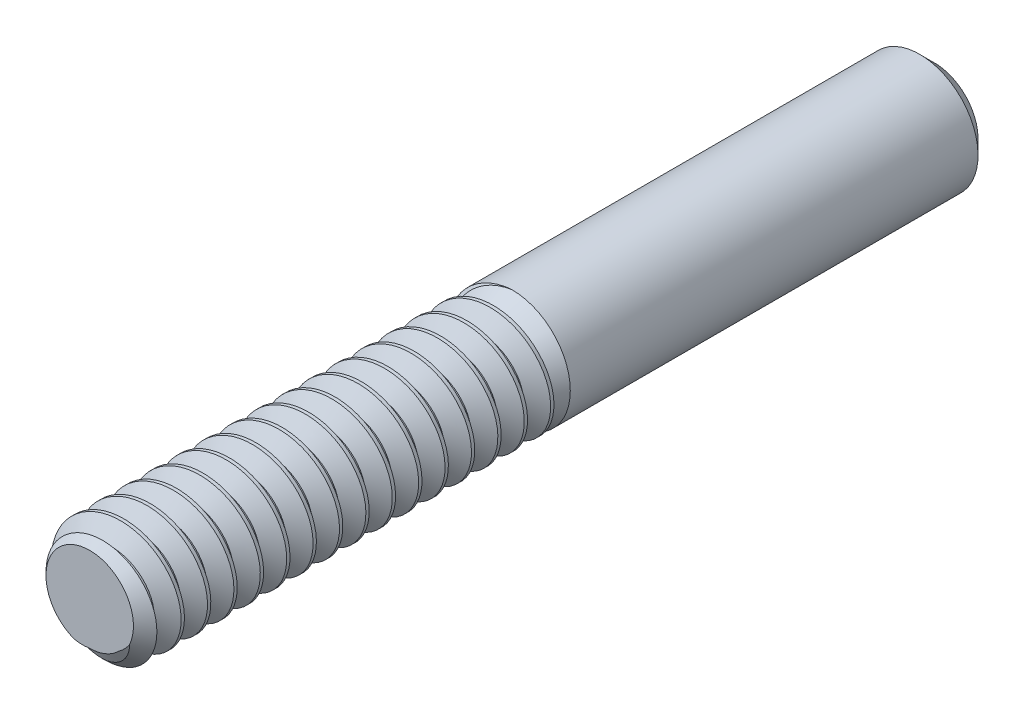
SolidWorks part; units mm, degrees
ref_plane "Front Plane" through (0, 0, 0) normal (0, 0, 1) x (1, 0, 0)
ref_plane "Top Plane" through (0, 0, 0) normal (0, 1, 0) x (1, 0, 0)
ref_plane "Right Plane" through (0, 0, 0) normal (1, 0, 0) x (0, 0, -1)
sketch "Sketch1" plane through (0, 0, 0) normal (1, 0, 0) x (0, 0, -1)
  line L0 (-12.7, 0) -> (12.7, 0) construction
  line L1 (12.7, 1.7526) -> (12.7, -1.7526) construction
  line L2 (-12.7, 1.7526) -> (-12.7, -1.7526) construction
  line L3 (0, 1.7526) -> (0, -1.7526) construction
  line L4 (-12.7, 1.7526) -> (-11.9063, 1.7526) construction
  line L5 (-12.7, -1.7526) -> (-10.7156, -1.7526) construction
  point P4 (12.7, 0)
  point P7 (-12.7, 0)
  point P8 (0, 0)
  point P11 (0, 0)
  point P13 (0, 0)
  point P17 (-10.7156, -1.7526)
  dimension "Length" = 25.4
  dimension "Thread Dia" = 3.5052
  dimension "Shaft Dia" = 3.5052
  dimension "Thread Length" = 12.7
  dimension "Shaft Length" = 12.7
  dimension "Pitch" = 0.7937
  dimension "D1" = 1.9844
sketch "Sketch2" plane through (0, 0, 0) normal (0, 0, 1) x (1, 0, 0)
  line L0 (-1.7526, 0) -> (1.7526, 0) construction
  line L1 (0, 1.7526) -> (0, -1.7526) construction
  circle A0 centre (0, 0) radius 1.7526 construction
  point P9 (0, 0)
  dimension "Shaft Dia" = 3.5052
sketch "Sketch3" plane through (0, 0, 0) normal (1, 0, 0) x (0, 0, -1)
  line L0 (-12.7, 0) -> (12.7, 0)
  line L1 (12.7, 0) -> (12.7, 1.7526)
  line L2 (12.7, 1.7526) -> (-12.7, 1.7526) construction
  line L3 (-12.7, 1.7526) -> (-12.7, 0)
  line L4 (-12.7, 1.7526) -> (0, 1.7526)
  line L5 (0, 1.7526) -> (12.7, 1.7526)
revolve "Revolve1" add sketch "Sketch3" angle 360 about L0
chamfer "Chamfer1" distance 0.4381 angle 45 1 edges at (0, -1.7526, 12.7)
chamfer "Chamfer2" distance 0.4381 angle 45 1 edges at (0, -1.7526, -12.7)
ref_plane "Plane1" through (0, 0, 0) normal (0, 0, 1) x (1, 0, 0)
sketch "Sketch4" plane through (0, 0, 12.7) normal (0, 0, 1) x (1, 0, 0)
  circle A0 centre (0, 0) radius 1.7526
curve "Helix/Spiral1" pitch 0.7937 height 13.4937 turns 17
split "Split1" trim tools "Plane1" bodies to split 104 resulting bodies 105 106
sketch "Sketch5" plane through (0, 0, 0) normal (1, 0, 0) x (0, 0, -1)
  line L0 (-13.4441, 1.8385) -> (-12.6504, 1.8385) construction
  line L1 (-12.6504, 1.8385) -> (-13.0473, 1.1511) construction
  line L2 (-13.0473, 1.1511) -> (-13.4441, 1.8385) construction
  line L3 (-13.4193, 1.7956) -> (-12.6752, 1.7956) construction
  line L4 (-13.3945, 1.7526) -> (-12.7, 1.7526) construction
  line L5 (-13.0969, 1.237) -> (-12.9977, 1.237) construction
  line L6 (-13.0473, 1.237) -> (-13.0473, 1.1511) construction
  line L7 (-13.0473, 1.7526) -> (-13.0473, 1.8385) construction
  line L8 (-13.4193, 1.7956) -> (-12.6752, 1.7956)
  line L9 (-12.6752, 1.7956) -> (-12.9977, 1.237)
  line L10 (-12.9977, 1.237) -> (-13.0969, 1.237)
  line L11 (-13.0969, 1.237) -> (-13.4193, 1.7956)
  point P12 (-13.0473, 1.7956)
  dimension "D1" = 0.7937
  dimension "D2" = 0.0992
sweep "Cut-Sweep1" cut profiles "Sketch5" path "Helix/Spiral1" align with end faces yes
sketch "Sketch6" plane through (0, 0, 0) normal (0, 0, 1) x (1, 0, 0)
  circle A1 centre (0, 0) radius 1.7526
  circle A2 centre (0, 0) radius 1.7526
  dimension "D1" = 0
extrude "Boss-Extrude1" add sketch "Sketch6" along normal through all draft 30
equation "\"D1@Chamfer1\"=\"Thread Dia@Sketch1\"*.125"
equation "\"D1@Chamfer2\"=\"Shaft Dia@Sketch1\"*.125"
equation "\"D3@Helix/Spiral1\"=\"Thread Length@Sketch1\"+\"Pitch@Sketch1\""
equation "\"D4@Helix/Spiral1\"=\"Pitch@Sketch1\""
equation "\"D2@Sketch5\"=\"D1@Sketch5\"/8"
equation "\"D1@Sketch5\"=\"Pitch@Sketch1\""
equation "\"D1@Sketch1\"=\"Pitch@Sketch1\"*2.5"
